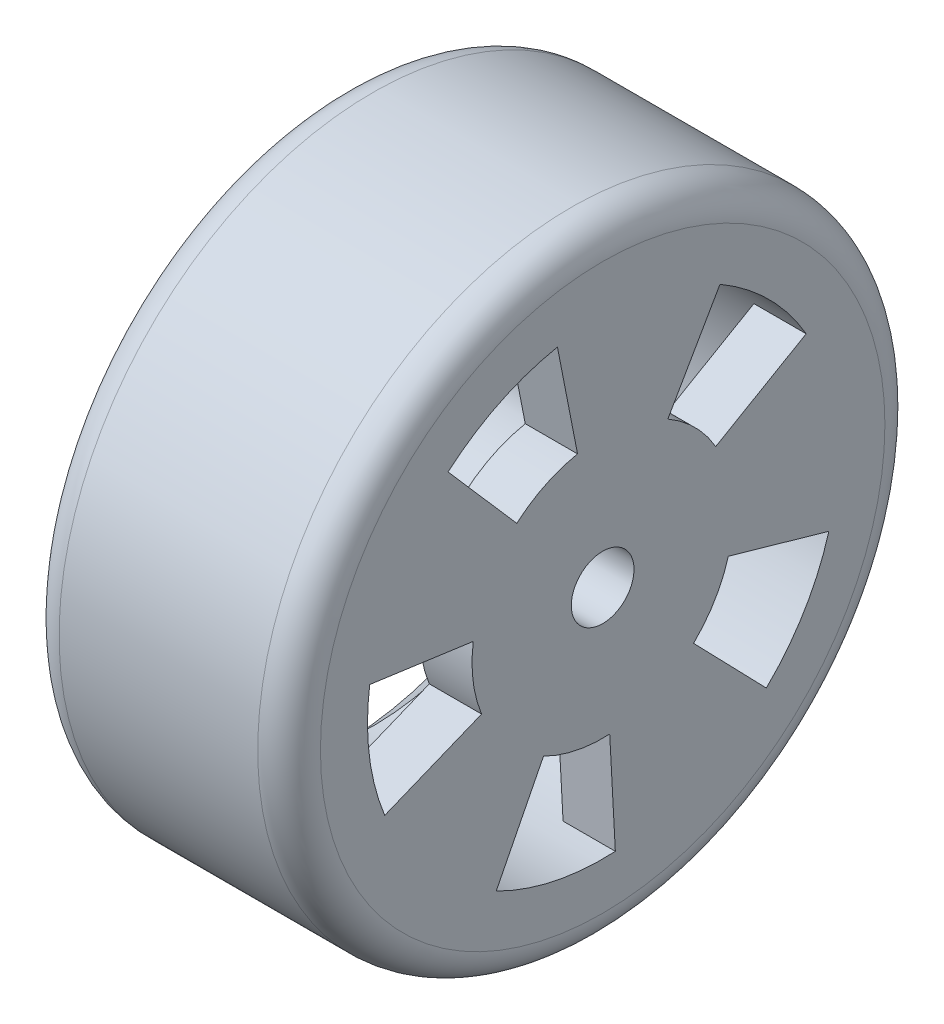
SolidWorks part; units mm, degrees
ref_plane "Front Plane" through (0, 0, 0) normal (0, 0, 1) x (1, 0, 0)
ref_plane "Top Plane" through (0, 0, 0) normal (0, 1, 0) x (1, 0, 0)
ref_plane "Right Plane" through (0, 0, 0) normal (1, 0, 0) x (0, 0, -1)
sketch "Sketch1" plane through (0, 0, 0) normal (1, 0, 0) x (0, 0, -1)
  circle A0 centre (0, 0) radius 30
  dimension "D1" = 60
extrude "Boss-Extrude1" add sketch "Sketch1" along normal blind 25
fillet "Fillet1" radius 3 2 edges at (0, 0, -30) (25, 0, -30)
sketch "Sketch3" plane through (0, 0, 0) normal (-1, 0, 0) x (0, 0, 1)
  circle A0 centre (0, 0) radius 22.5
  dimension "D1" = 45
extrude "Cut-Extrude1" cut sketch "Sketch3" against normal blind 20
chamfer "Chamfer1" distance 3 angle 45 1 edges at (0, 0, 22.5)
sketch "Sketch2" plane through (25, 0, 0) normal (-1, 0, 0) x (0, 0, 1)
  line L0 (-6.2332, 10.835) -> (-11.2197, 19.503)
  line L1 (-10.8156, 6.2668) -> (-19.4681, 11.2803)
  line L2 (-10.8156, 6.2668) -> (0, 0) construction
  line L3 (0, 0) -> (-6.2332, 10.835) construction
  arc A0 (-6.2332, 10.835) -> (-10.8156, 6.2668) centre (0, 0) ccw
  arc A1 (-11.2197, 19.503) -> (-19.4681, 11.2803) centre (0, 0) ccw
  dimension "D1" = 25
  dimension "D2" = 45
  dimension "D3" = 30
extrude "Cut-Extrude2" cut sketch "Sketch2" along normal through all
pattern_circular "CirPattern1" count 5 every 71 about axis through (25, 0, 0) along (1, 0, 0) of "Cut-Extrude2"
sketch "Sketch4" plane through (20, 0, 0) normal (-1, 0, 0) x (0, 0, 1)
  circle A0 centre (0, 0) radius 10
  dimension "D1" = 20
extrude "Boss-Extrude2" add sketch "Sketch4" along normal blind 15
sketch "Sketch5" plane through (5, 0, 0) normal (-1, 0, 0) x (0, 0, 1)
  circle A0 centre (0, 0) radius 3
  dimension "D1" = 6
extrude "Cut-Extrude3" cut sketch "Sketch5" against normal through all
sketch "Sketch6" plane through (0, 0, 0) normal (0, 1, 0) x (1, 0, 0)
  line L0 (12.5, 0) -> (0, 0) construction
  circle A0 centre (12.5, 0) radius 2
  dimension "D2" = 4
  dimension "D1" = 12.5
extrude "Cut-Extrude4" cut sketch "Sketch6" against normal through all
ref_plane "Plane1" through (0, -20, 0) normal (0, 1, 0) x (1, 0, 0)
sketch "Sketch7" plane through (0, -20, 0) normal (0, 1, 0) x (1, 0, 0)
  circle A0 centre (12.5, 0) radius 4
  dimension "D1" = 8
extrude "Cut-Extrude5" cut sketch "Sketch7" against normal through all
